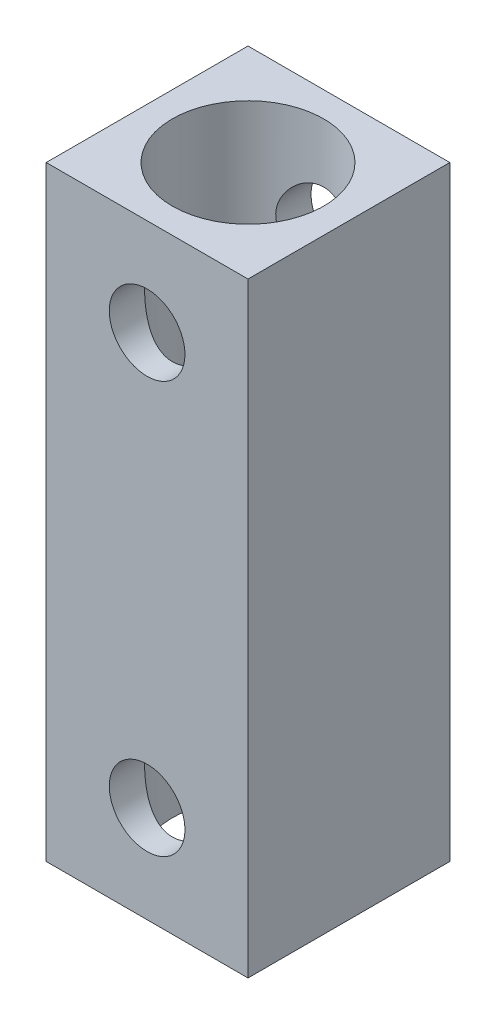
SolidWorks part; units mm, degrees
ref_plane "Front Plane" through (0, 0, 0) normal (0, 0, 1) x (1, 0, 0)
ref_plane "Top Plane" through (0, 0, 0) normal (0, 1, 0) x (1, 0, 0)
ref_plane "Right Plane" through (0, 0, 0) normal (1, 0, 0) x (0, 0, -1)
sketch "Sketch1" plane through (0, 0, 0) normal (0, 1, 0) x (1, 0, 0)
  line L1 (-4, -4) -> (4, -4)
  line L2 (-4, -4) -> (-4, 4)
  line L3 (-4, 4) -> (4, 4)
  line L4 (4, -4) -> (4, 4)
  line L5 (-4, -4) -> (4, 4) construction
  line L6 (-4, 4) -> (4, -4) construction
  circle A0 centre (0, 0) radius 3
  point P0 (0, 0)
  dimension "D2" = 6
  dimension "D1" = 8
extrude "Boss-Extrude1" add sketch "Sketch1" along normal blind 24
sketch "Sketch2" plane through (0, 0, -4) normal (0, 0, -1) x (-1, 0, 0)
  line L0 (4, 12) -> (-4, 12) construction
  line L1 (4, 24) -> (4, 0) construction
  line L2 (-4, 24) -> (-4, 0) construction
  circle A0 centre (0, 3.8413) radius 1.5
  circle A1 centre (0, 20.1587) radius 1.5
  point P10 (0, 4.0136)
  point P11 (0, 4.3195)
  point P12 (0, 0)
  point P13 (0, 4.1822)
  point P14 (0, 3.8413)
  point P15 (0, 5.5217)
  dimension "D1" = 3
extrude "Cut-Extrude1" cut sketch "Sketch2" against normal through all
